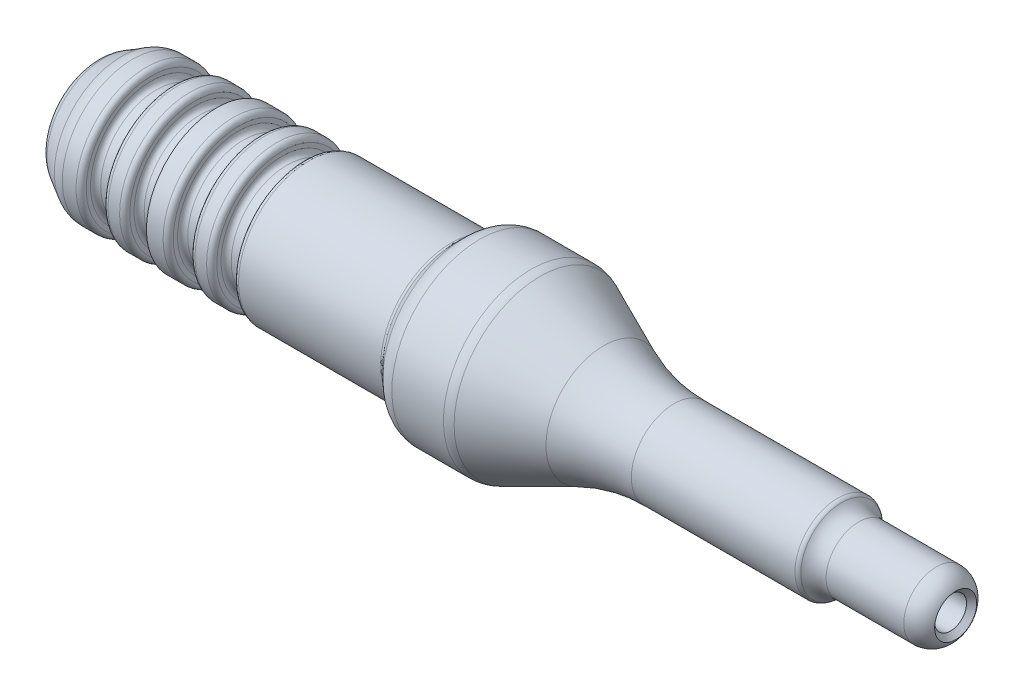
SolidWorks part; units mm, degrees
ref_plane "Front Plane" through (0, 0, 0) normal (0, 0, 1) x (1, 0, 0)
ref_plane "Top Plane" through (0, 0, 0) normal (0, 1, 0) x (1, 0, 0)
ref_plane "Right Plane" through (0, 0, 0) normal (1, 0, 0) x (0, 0, -1)
sketch "Sketch1" plane through (0, 0, 0) normal (0, 0, 1) x (1, 0, 0)
  line L0 (0, 0) -> (0, 3.52)
  line L1 (0, 3.52) -> (2.3, 4.8479)
  line L2 (2.3, 4.8479) -> (24.8, 4.8479)
  line L3 (24.8, 4.8479) -> (26, 6.0479)
  line L4 (26, 6.0479) -> (30.5, 6.0479)
  line L5 (30.5, 6.0479) -> (37.5, 2.9474)
  line L6 (37.5, 2.9474) -> (51.5, 2.9474)
  line L7 (51.5, 2.9474) -> (51.9026, 2.25)
  line L8 (51.9026, 2.25) -> (59.4526, 2.25)
  line L9 (59.4526, 2.25) -> (59.4526, 0)
  line L10 (0, 0) -> (59.4526, 0)
  point P4 (47.4618, 1.4553)
  dimension "D1" = 3.52
  dimension "D2" = 30
  dimension "D3" = 2.3
  dimension "D4" = 22.5
  dimension "D5" = 45
  dimension "D6" = 1.2
  dimension "D7" = 4.5
  dimension "D8" = 7
  dimension "D9" = 156.11
  dimension "D10" = 120
  dimension "D11" = 7.55
  dimension "D12" = 14
  dimension "D13" = 2.25
revolve "Revolve1" add sketch "Sketch1" angle 360 about L10
sketch "Sketch2" plane through (0, 0, 0) normal (0, 0, 1) x (1, 0, 0)
  line L0 (0, 2.25) -> (33.5, 2.25)
  line L1 (0, 3.52) -> (0, -3.52) construction
  line L2 (33.5, 2.25) -> (35.4919, 1.1)
  line L3 (35.4919, 1.1) -> (59.4526, 1.1)
  line L4 (59.4526, -2.25) -> (59.4526, 2.25) construction
  line L5 (0, 2.25) -> (0, 0)
  line L6 (0, 0) -> (59.4526, 0)
  line L7 (59.4526, 0) -> (59.4526, 1.1)
  line L8 (7, 3.85) -> (8.5, 3.85)
  line L9 (4, 4.85) -> (5.5, 4.85)
  line L10 (4, 4.85) -> (4, 3.85)
  line L11 (4, 3.85) -> (5.5, 3.85)
  line L12 (5.5, 4.85) -> (5.5, 3.85)
  line L13 (7, 4.85) -> (7, 3.85)
  line L14 (7, 4.85) -> (8.5, 4.85)
  line L15 (8.5, 4.85) -> (8.5, 3.85)
  line L16 (10, 3.85) -> (11.5, 3.85)
  line L17 (10, 4.85) -> (10, 3.85)
  line L18 (10, 4.85) -> (11.5, 4.85)
  line L19 (11.5, 4.85) -> (11.5, 3.85)
  line L20 (13, 3.85) -> (14.5, 3.85)
  line L21 (13, 4.85) -> (13, 3.85)
  line L22 (13, 4.85) -> (14.5, 4.85)
  line L23 (14.5, 4.85) -> (14.5, 3.85)
  point P4 (7, 4.35)
  dimension "D1" = 2.25
  dimension "D2" = 150
  dimension "D3" = 1.1
  dimension "D4" = 33.5
  dimension "D5" = 1.5
  dimension "D6" = 1
  dimension "D7" = 4
  dimension "D8" = 4.85
  dimension "D10" = 1.5
  dimension "D9" = 4
revolve "Cut-Revolve1" cut sketch "Sketch2" angle 360 about L6
fillet "Fillet1" radius 12 1 edges at (37.5, -2.9474, 0)
chamfer "Chamfer1" distance 0.35 angle 45 2 edges at (59.4526, 0, 1.1) (0, 0, 2.25)
fillet "Fillet2" radius 1.5 6 edges at (51.9026, -2.25, 0) (2.3, -4.8479, 0) (0, -3.52, 0) (30.5, -6.0479, 0) (26, -6.0479, 0) (59.4526, -2.25, 0)
fillet "Fillet3" radius 0.35 17 edges at (10, 0, -4.8479) (13, 0, 3.85) (14.5, 0, 3.85) (13, 0, -4.8479) (11.5, 0, 4.8479) (10, 0, 3.85) (11.5, 0, 3.85) (7, 0, 3.85) (8.5, 0, 3.85) (7, 0, -4.8479) (5.5, 0, 4.8479) (51.5, -2.9474, 0) (24.8, -4.8479, 0) (14.5, 0, 4.8479) (5.5, 0, 3.85) (4, 0, 3.85) (4, 0, -4.8479)
